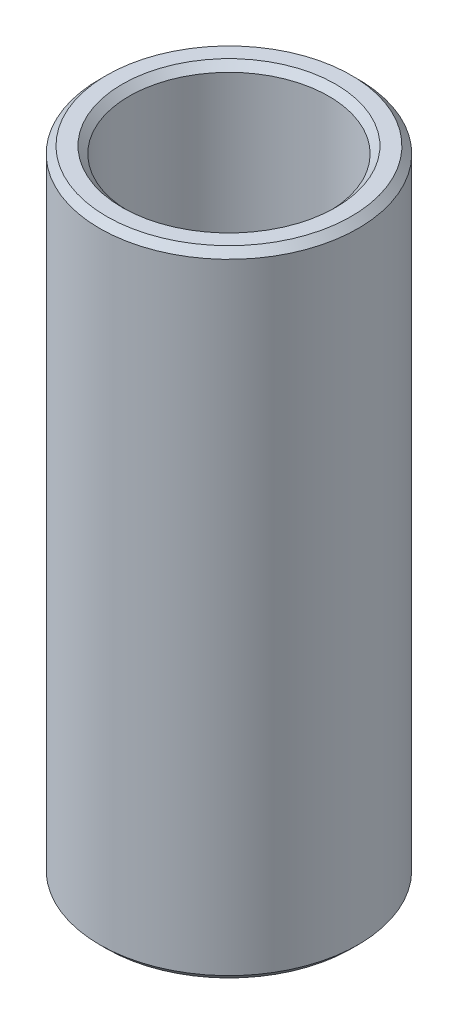
SolidWorks part; units mm, degrees
ref_plane "Front Plane" through (0, 0, 0) normal (0, 0, 1) x (1, 0, 0)
ref_plane "Top Plane" through (0, 0, 0) normal (0, 1, 0) x (1, 0, 0)
ref_plane "Right Plane" through (0, 0, 0) normal (1, 0, 0) x (0, 0, -1)
sketch "Sketch1" plane through (0, 0, 0) normal (0, 1, 0) x (1, 0, 0)
  circle A0 centre (0, 0) radius 47.5
  dimension "SLEEVE_OD" = 95
extrude "Boss-Extrude1" add sketch "Sketch1" along normal blind 233.0522
sketch "Sketch2" plane through (0, 0, 0) normal (0, 1, 0) x (1, 0, 0)
  circle A0 centre (0, 0) radius 36.6939
  dimension "BORE_D" = 73.3878
extrude "Cut-Extrude1" cut sketch "Sketch2" along normal through all
chamfer "Chamfer1" distance 2.5467 angle 45 4 edges at (0, 233.0522, 36.6939) (0, 0, 36.6939) (0, 0, 47.5) (0, 233.0522, 47.5)
